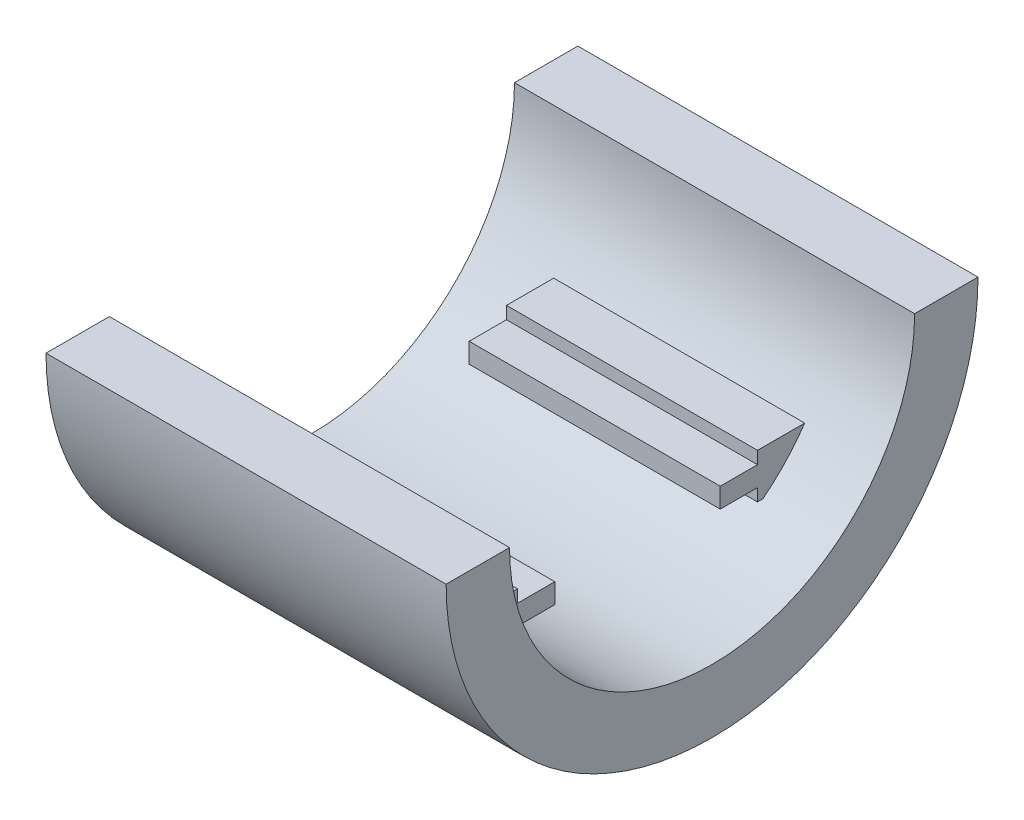
SolidWorks part; units mm, degrees
ref_plane "Front Plane" through (0, 0, 0) normal (0, 0, 1) x (1, 0, 0)
ref_plane "Top Plane" through (0, 0, 0) normal (0, 1, 0) x (1, 0, 0)
ref_plane "Right Plane" through (0, 0, 0) normal (1, 0, 0) x (0, 0, -1)
sketch "Sketch1" plane through (0, 0, 0) normal (0, 1, 0) x (1, 0, 0)
  line L1 (0, 0) -> (40.894, 0)
  line L2 (0, 0) -> (0, -27.178)
  line L3 (0, -27.178) -> (40.894, -27.178)
  line L4 (40.894, 0) -> (40.894, -27.178)
  dimension "D1" = 40.894
  dimension "D2" = 27.178
revolve "Revolve1" add sketch "Sketch1" angle 180 about L1
sketch "Sketch2" plane through (0, 0, 0) normal (0, 1, 0) x (1, 0, 0)
  line L1 (0, 0) -> (41.402, 0)
  line L2 (0, 0) -> (0, -20.701)
  line L4 (41.402, 0) -> (41.402, -20.701)
  line L5 (1.27, -20.701) -> (40.132, -20.701)
  line L8 (1.27, -20.701) -> (0, -20.701)
  line L9 (40.132, -20.701) -> (41.402, -20.701)
  line L10 (0, 0) -> (0, -21.971) construction
  line L11 (0, -21.971) -> (41.402, -21.971) construction
  line L12 (41.402, 0) -> (41.402, -21.971) construction
  line L13 (1.27, -1.27) -> (40.132, -1.27) construction
  line L14 (40.132, -1.27) -> (40.132, -20.701) construction
  line L15 (1.27, -1.27) -> (1.27, -20.701) construction
  dimension "D1" = 1.27
revolve "Cut-Revolve1" cut sketch "Sketch2" angle 360 about L1
sketch "Sketch3" plane through (0, 0, 0) normal (0, 0, 1) x (1, 0, 0)
  line L0 (40.894, -20.701) -> (40.894, 0) construction
  line L1 (33.274, -11.684) -> (7.62, -11.684)
  line L2 (33.274, -11.684) -> (33.274, -16.256)
  line L3 (33.274, -16.256) -> (7.62, -16.256)
  line L4 (7.62, -11.684) -> (7.62, -16.256)
  line L5 (40.894, 0) -> (0, 0) construction
  dimension "D1" = 7.62
  dimension "D2" = 7.62
  dimension "D3" = 4.572
  dimension "D4" = 11.684
extrude "Boss-Extrude1" add sketch "Sketch3" along normal up to surface and the other way up to surface up to face at (20.447, -10.3505, 0) other way up to face at (20.447, -10.3505, 0)
sketch "Sketch4" plane through (0, -11.684, 0) normal (0, 1, 0) x (1, 0, 0)
  line L0 (33.274, -17.0885) -> (33.274, 17.0885) construction
  line L1 (33.274, -12.2625) -> (7.62, -12.2625)
  line L2 (33.274, -12.2625) -> (33.274, 12.2625)
  line L3 (33.274, 12.2625) -> (7.62, 12.2625)
  line L4 (7.62, -12.2625) -> (7.62, 12.2625)
  line L5 (7.62, -17.0885) -> (7.62, 17.0885) construction
  line L6 (33.274, -17.0885) -> (7.62, -17.0885) construction
  line L7 (33.274, 17.0885) -> (7.62, 17.0885) construction
  dimension "D1" = 4.826
  dimension "D2" = 4.826
extrude "Cut-Extrude1" cut sketch "Sketch4" against normal blind 4.572
sketch "Sketch5" plane through (7.62, 0, 0) normal (-1, 0, 0) x (0, 0, 1)
  line L0 (-12.2625, -16.256) -> (-12.2625, -11.684) construction
  line L1 (-12.2625, -12.954) -> (-8.4525, -12.954)
  line L2 (-12.2625, -12.954) -> (-12.2625, -14.986)
  line L3 (-12.2625, -14.986) -> (-8.4525, -14.986)
  line L4 (-8.4525, -12.954) -> (-8.4525, -14.986)
  line L5 (12.2625, -16.256) -> (12.2625, -11.684) construction
  line L6 (12.2625, -12.954) -> (8.4525, -12.954)
  line L7 (12.2625, -12.954) -> (12.2625, -14.986)
  line L8 (12.2625, -14.986) -> (8.4525, -14.986)
  line L9 (8.4525, -12.954) -> (8.4525, -14.986)
  line L10 (17.0885, -11.684) -> (12.2625, -11.684) construction
  line L11 (-12.2625, -11.684) -> (-17.0885, -11.684) construction
  dimension "D1" = 2.032
  dimension "D2" = 3.81
  dimension "D3" = 1.27
  dimension "D4" = 1.27
  dimension "D5" = 2.032
  dimension "D6" = 3.81
extrude "Boss-Extrude2" add sketch "Sketch5" against normal up to surface (25.654 mm away) up to face at (33.274, -14.0106, -13.651)
